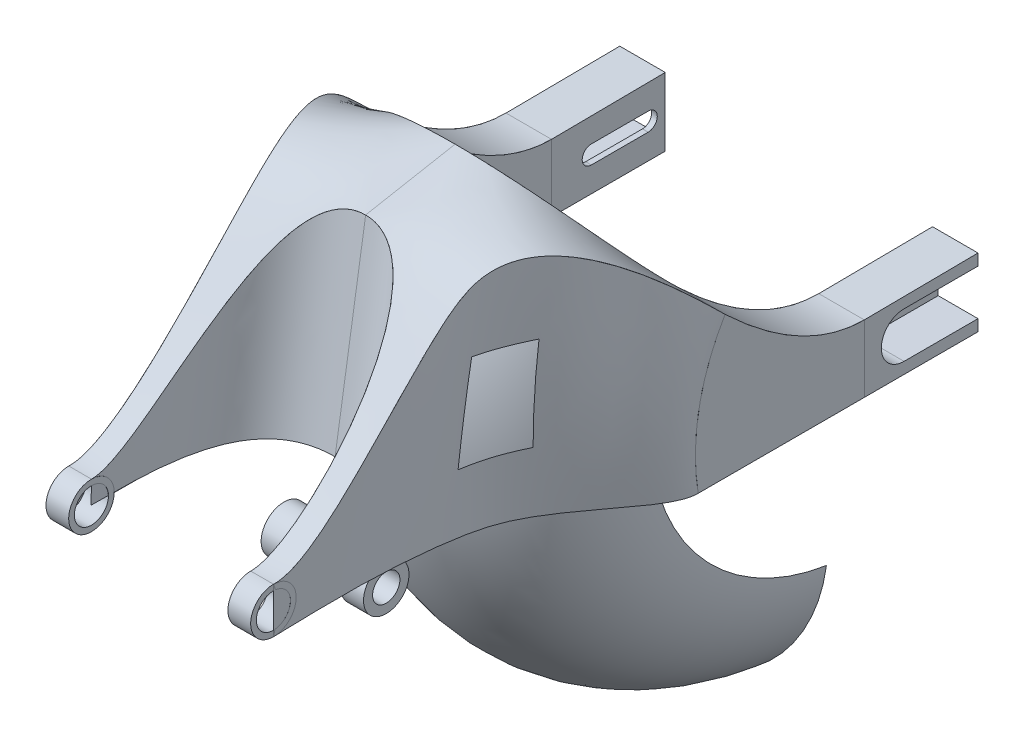
SolidWorks part; units mm, degrees
note: '?' marks a value the reader was unsure of. The reader was unsure of these and kept them because the rebuilt part matched: shared geometry of "Szkic - insert - tylne koło<6>", "Baza - płaszczyzna prawa<3>".
ref_plane "Płaszczyzna przednia" through (0, 0, 0) normal (0, 0, 1) x (1, 0, 0)
ref_plane "Płaszczyzna górna" through (0, 0, 0) normal (0, 1, 0) x (1, 0, 0)
ref_plane "Płaszczyzna prawa" through (0, 0, 0) normal (1, 0, 0) x (0, 0, -1)
sketch "Baza - płaszczyzna prawa" plane through (0, 0, 0) normal (1, 0, 0) x (0, 0, -1)
  line L0 (0, 0) -> (512, 0) construction
  line L1 (0, 0) -> (512, 0) construction
  line L2 (144.2, 0) -> (144.2, -77) construction
  line L3 (90, 0) -> (90, 100) construction
  line L4 (200, 0) -> (200, 140) construction
  arc A2 (440.6668, 297.4126) -> (440.6668, -297.4126) centre (487, 0) ccw
  dimension "D3" = 90
  dimension "D4" = 100
  dimension "D5" = 301
  dimension "D1" = 77
  dimension "D2" = 144.2
  dimension "D6" = 200
  dimension "D7" = 140
sketch "Szkic1" plane through (0, 0, 0) normal (0, 1, 0) x (1, 0, 0)
  line L0 (0, 0) -> (0, 512) construction
  line L1 (0, 0) -> (0, 512) construction
  line L2 (117.5, 186) -> (-117.5, 186) construction
  line L3 (117.5, 186) -> (-117.5, 186) construction
  arc A0 (-89, 275) -> (89, 275) centre (0, 275) ccw
  point P7 (0, 186)
  dimension "D1" = 89
  dimension "D2" = 89
sketch "Baza - płaszczyzna górna" plane through (0, 0, 0) normal (0, 1, 0) x (1, 0, 0)
  line L0 (0, 0) -> (0, 512) construction
  line L1 (117.5, 144.2) -> (-117.5, 144.2) construction
  line L2 (135, 0) -> (-135, 0) construction
  line L3 (-117.5, 512) -> (117.5, 512) construction
  line L4 (-117.5, 512) -> (-117.5, 144.2) construction
  line L5 (117.5, 512) -> (117.5, 144.2) construction
  line L6 (117.5, 186) -> (-117.5, 186) construction
  line L7 (135, 22.5) -> (135, -22.5) construction
  line L8 (-135, 22.5) -> (-135, -22.5) construction
  line L9 (117.5, 512) -> (125, 512) construction
  line L10 (125, 512) -> (125, 144.2) construction
  line L11 (125, 144.2) -> (117.5, 144.2) construction
  point P2 (0, 487)
  point P7 (0, 0)
  point P10 (0, 512)
  point P12 (0, 144.2)
  point P16 (135, 0)
  dimension "D1" = 512
  dimension "D2" = 144.2
  dimension "D3" = 270
  dimension "D4" = 235
  dimension "D5" = 326
  dimension "D6" = 45
  dimension "D7" = 25
  dimension "D8" = 125
ref_plane "Powierzchnia styku z ramą" through (135, 0, 0) normal (1, 0, 0) x (0, 0, -1)
sketch "Szkic - insert - rama" plane through (135, 0, 0) normal (1, 0, 0) x (0, 0, -1)
  circle A0 centre (0, 0) radius 20
  circle A1 centre (0, 0) radius 15
  dimension "D1" = 40
  dimension "D2" = 30
ref_plane "Powierzchnia graniczna koła" through (125, 0, 0) normal (1, 0, 0) x (0, 0, -1)
ref_plane "Płaszczyzna pracy łańcucha" through (100, 0, 0) normal (1, 0, 0) x (0, 0, -1)
sketch "Łańcuch - baza" plane through (100, 0, 0) normal (1, 0, 0) x (0, 0, -1)
  line L0 (0, 0) -> (-72.2803, -23.4853) construction
  line L1 (0, 0) -> (512, 0) construction
  line L2 (0, 0) -> (-217.9404, 0) construction
  line L3 (0, 0) -> (-217.562, -40.3227) construction
  dimension "D1" = 76
  dimension "D2" = 162
  dimension "D3" = 10.5
sketch "Łańcuch - zarys" plane through (100, 0, 0) normal (1, 0, 0) x (0, 0, -1)
  line L0 (-75.0403, -1.6591) -> (502.9674, 71.4312)
  line L1 (-83.7478, 33.3697) -> (482.2437, 147.529)
  line L2 (-72.2803, -23.4853) -> (512, 0) construction
  line L3 (-79.1476, -81.0773) -> (494.1805, -149.4413)
  line L4 (-73.2796, -45.4626) -> (508.7296, -71.9257)
  circle A0 centre (-72.2803, -23.4853) radius 22
  circle A1 centre (512, 0) radius 72
  arc A2 (-83.7478, 33.3697) -> (-79.1476, -81.0773) centre (-72.2803, -23.4853) ccw
  arc A3 (494.1805, -149.4413) -> (482.2437, 147.529) centre (512, 0) ccw
  point P0 (-72.2803, -23.4853)
  point P2 (512, 0)
  dimension "D1" = 44
  dimension "D2" = 144
  dimension "D3" = 116
  dimension "D4" = 301
sketch "Szkic otwór łańcuch" plane through (0, 0, 0) normal (0, 0, 1) x (1, 0, 0)
  line L3 (100, -130) -> (110, -130)
  line L13 (115, -125) -> (115, -45)
  line L14 (110, -40) -> (100, -40)
  line L15 (95, -45) -> (95, -125)
  arc A0 (100, -130) -> (95, -125) centre (100, -125) cw
  arc A1 (110, -130) -> (115, -125) centre (110, -125) ccw
  arc A2 (115, -45) -> (110, -40) centre (110, -45) ccw
  arc A3 (100, -40) -> (95, -45) centre (100, -45) ccw
  dimension "D1" = 5
  dimension "D2" = 95
  dimension "D3" = 20
  dimension "D4" = 40
  dimension "D5" = 90
surface "Opona"
ref_axis "Oś tynego koła" through (-117.5, 0, -512) along (1, 0, 0)?
ref_axis "Oś mocowania do ramy" through (135, 0, 0) along (-1, 0, 0)?
ref_axis "Oś mocowania linkage" through (0, -77, -144.2) along (1, 0, 0)?
sketch "Szkic - insert - linkage" plane through (0, 0, 0) normal (1, 0, 0) x (0, 0, -1)
  circle A0 centre (144.2, -77) radius 12
  circle A1 centre (144.2, -77) radius 20
  dimension "D1" = 40
  dimension "D2" = 24
sketch "Szkic - insert - tylne koło" plane through (125, 0, 0) normal (1, 0, 0) x (0, 0, -1)
  line L0 (487, 20) -> (552, 20)
  line L1 (512, 0) -> (144.2, 0) construction
  line L2 (487, -20) -> (552, -20)
  line L3 (537, 8) -> (487, 8)
  line L4 (537, -8) -> (487, -8)
  line L6 (552, -30) -> (552, -20)
  line L7 (552, -30) -> (452, -30)
  line L8 (452, -30) -> (452, 29.0445)
  line L9 (452, 29.0445) -> (552, 30)
  line L11 (552, 20) -> (552, -20)
  line L12 (552, 20) -> (552, 30)
  arc A1 (487, 8) -> (487, -8) centre (487, 0) ccw
  arc A2 (537, -8) -> (537, 8) centre (537, 0) ccw
  arc A3 (487, 20) -> (487, -20) centre (487, 0) ccw
  dimension "D1" = 40
  dimension "D3" = 8
  dimension "D2" = 65
  dimension "D4" = 487
  dimension "D5" = 537
  dimension "D6" = 60
  dimension "D7" = 10
  dimension "D8" = 100
  dimension "D9" = 29.0445
extrude "Tylne koło" add sketch "Szkic - insert - tylne koło" along normal blind 5 from offset 7.5 separate body contours A3 L0 L12 L9 L8 L7 L6 L2 | L0 A3 L2 L11 A2 L4 A1 L3 offset against normal yes
extrude "Tylene koło 2" add sketch "Szkic - insert - tylne koło<6>" along normal blind 35 from offset 2.5 contours A3 L0 L12 L9 L8 L7 L6 L2 offset against normal yes
sketch "Szkic - insert - tylne koło<6>" plane through (125, 0, 0) normal (1, 0, 0) x (0, 0, -1) same geometry as "Szkic - insert - tylne koło"
extrude "Rama" add sketch "Szkic - insert - rama" against normal mid plane 20 from offset 55 offset against normal yes
extrude "Linkage" add sketch "Szkic - insert - linkage" along normal blind 20 from offset 25 separate body
sketch "Szkic2" plane through (0, 0, 0) normal (0, 1, 0) x (1, 0, 0)
  line L0 (0, 0) -> (0, 512) construction
  line L1 (117.5, 144.2) -> (-117.5, 144.2) construction
  line L2 (117.5, 512) -> (117.5, 144.2) construction
  line L3 (0, 0) -> (0, 512) construction
  line L4 (117.5, 144.2) -> (-117.5, 144.2) construction
  line L5 (117.5, 512) -> (117.5, 144.2) construction
  line L6 (117.5, 186) -> (-117.5, 186) construction
  line L7 (117.5, 186) -> (-117.5, 186) construction
  line L8 (-117.5, 512) -> (-117.5, 144.2) construction
  arc A0 (117.5, 303.5) -> (-117.5, 303.5) centre (0, 303.5) cw
  point P7 (0, 186)
  dimension "D1" = 117.5
surface "Powierzchnia-Wyciągnięcie po ścieżce2"
sketch "Baza - płaszczyzna prawa<3>" plane through (0, 0, 0) normal (1, 0, 0) x (0, 0, -1) same geometry as "Baza - płaszczyzna prawa"
sketch "Szkic3" plane through (0, 0, 0) normal (1, 0, 0) x (0, 0, -1)
  line L0 (419.4442, 29.0445) -> (484.5558, 29.0445) construction
  arc A1 (440.6668, 297.4126) -> (440.6668, -297.4126) centre (487, 0) ccw construction
  spline S1 degree 2 poles (452, 29.0445) (369.4923, 29.0445) (249.7477, 185.2359) knots 0 0 0 1 1 1
ref_plane "Płaszczyzna1" through (117.5, 0, 0) normal (1, 0, 0) x (0, 0, -1)
surface "Powierzchnia-Przytnij2"
sketch "Szkic8" plane through (117.5, 0, 0) normal (1, 0, 0) x (0, 0, -1)
  line L0 (452, 29.0445) -> (452, -30)
  line L1 (452, -30) -> (305.9689, -30)
  arc A0 (329.6558, 94.4196) -> (458.7537, -181.313) centre (487, 0) ccw construction
  arc A1 (329.6558, 94.4196) -> (305.9689, -30) centre (487, 0) ccw
  parabola Q0 (452, 29.0445) -> (249.7477, 185.2359) focus (461.832, 70.285) apex (471.1352, 31.2625) construction
  parabola Q1 (452, 29.0445) -> (329.6558, 94.4196) focus (461.832, 70.285) apex (471.1352, 31.2625)
surface "Powierzchnia-wypełnij2" sketch "Szkic8"
sketch "Szkic9" plane through (0, 0, 0) normal (1, 0, 0) x (0, 0, -1)
  line L0 (249.7477, 185.2359) -> (171.0873, 170.657)
  line L1 (0, 0) -> (-217.562, -40.3227) construction
  dimension "D1" = 80
sketch "Szkic10" plane through (0, 0, 0) normal (0, 1, 0) x (1, 0, 0)
  line L0 (135, 0) -> (-135, 0) construction
  line L1 (0, 0) -> (0, 512) construction
  line L2 (-43.7231, 144.2) -> (43.7231, 144.2) construction
  line L3 (70.3601, 49.3384) -> (70.3601, -49.3384) construction
  spline S0 degree 3 poles (70.3601, 0) (70.3601, 61.6729) (70.9337, 144.2) (0, 144.2) knots 0 0 0 0 1 1 1 1
sketch3d "Szkic 3D4"
  line L0 (70, 19.9999, 58.624) -> (70, 19.9999, -58.7244) construction
  line L1 (40.0167, 170.657, -171.0873) -> (-138.045, 170.657, -171.0873) construction
  circle A1 centre (70, 0, 0) radius 20 construction
  spline S0 degree 3 poles (0, 170.657, -171.0873) (77.42, 170.657, -171.0873) (70, 19.9999, -48.9453) (70, 19.9999, -0.0502) knots 0 0 0 0 1 1 1 1
  point P7 (90, 0, 0)
ref_plane "Płaszczyzna2" through (70, 0, 0) normal (1, 0, 0) x (0, 0, -1)
sketch "Szkic11" plane through (70, 0, 0) normal (1, 0, 0) x (0, 0, -1)
  line L0 (0, 0) -> (0.0502, 19.9999)
sketch "Szkic12" plane through (0, 0, 0) normal (1, 0, 0) x (0, 0, -1)
  line L0 (144.2, 0) -> (171.0873, 170.657)
other "Granica-Powierzchnia2"
sketch "Szkic13" plane through (117.5, 0, 0) normal (1, 0, 0) x (0, 0, -1)
  line L0 (305.9689, -30) -> (452, -30) construction
  line L1 (305.9689, -30) -> (452, -30)
  parabola Q0 (452, 29.0445) -> (329.6558, 94.4196) focus (461.832, 70.285) apex (471.1352, 31.2625) construction
  parabola Q1 (452, 29.0445) -> (329.6558, 94.4196) focus (461.832, 70.285) apex (471.1352, 31.2625)
surface "Powierzchnia-Wyciągnięcie1" sketch "Szkic13" parameters "D1"=40
surface "Powierzchnia-Odsunięcie1" parameters "D1"=40
sketch3d "Szkic 3D5"
  line L2 (90, 19.9999, -0.0626) -> (70, 19.9999, -0.0502)
  circle A0 centre (90, 0, 0) radius 20 construction
  spline S0 degree 3 poles (90, 19.9999, -0.0626) (90.2116, 18.5249, -38.5786) (86.5392, 117.6214, -119.1846) (95.028, 203.5135, -219.9128) (157.9714, 125.2072, -298.1714) (157.5, 94.4196, -329.6558) knots 0 0 0 0 0.38002 0.48002 1 1 1 1
  point P2 (90, 19.9999, -0.0626)
  point P11 (110, 0, 0)
sketch3d "Szkic 3D6"
  line L0 (101.7603, 170.3306, -205.3562) -> (0, 176.8832, -204.6804)
  line L1 (0, 185.2359, -249.7477) -> (0, 170.657, -171.0873) construction
  spline S1 degree 3 poles (90, 19.9999, -0.0626) (90.2116, 18.5249, -38.5786) (86.5392, 117.6214, -119.1846) (95.028, 203.5135, -219.9128) (157.9714, 125.2072, -298.1714) (157.5, 94.4196, -329.6558) knots 0 0 0 0 0.38002 0.48002 1 1 1 1 construction
  point P2 (0, 0, 0)
  point P3 (0, 0, 0)
  point P4 (0, 0, 0)
  point P9 (0, 0, 0)
  point P10 (101.7541, 170.3303, -205.3587)
surface "Powierzchnia-wypełnij3"
sketch3d "Szkic 3D7"
  line L0 (0, 0, 0) -> (0, -24.2309, 0) construction
  circle A0 centre (90, 0, 0) radius 20 construction
  spline S0 degree 3 poles (90, -20, -0.0286) (90.2018, -19.3803, -28.9179) (85.7177, -19.4542, -106.3396) (105.2605, -23.2237, -223.4276) (158.3459, -30.1687, -280.666) (157.5, -30, -305.9689) knots 0 0 0 0 0.507062 0.607062 1 1 1 1
  point P2 (90, -19.9998, -0.0992)
  point P4 (0, 0, 0)
  point P5 (90, -20, -0.0286)
  point P8 (110, 0, 0)
sketch3d "Szkic 3D8"
  line L0 (90, -20, -0.0286) -> (90, 20, -0.0286)
  circle A0 centre (90, 0, 0) radius 20 construction
  point P5 (110, 0, 0)
surface "Powierzchnia-Wyciągnięcie po profilach1"
sketch "Szkic14" plane through (0, 0, 0) normal (0, 0, 1) x (1, 0, 0)
  line L0 (100, -150.5) -> (100, 150.5) construction
  line L1 (100, -150.5) -> (100, 150.5) construction
  line L3 (94, 30) -> (110, 30)
  line L4 (94, 30) -> (94, 110)
  line L5 (94, 110) -> (110, 110)
  line L6 (110, 30) -> (110, 110)
  dimension "D1" = 16
  dimension "D2" = 6
  dimension "D3" = 80
  dimension "D4" = 30
surface "Powierzchnia-Przytnij3"
mirror "Lustro1" about plane through (0, 0, 0) normal (1, 0, 0) of bodies 216 103 104 230 232 223 225 228 229 227
